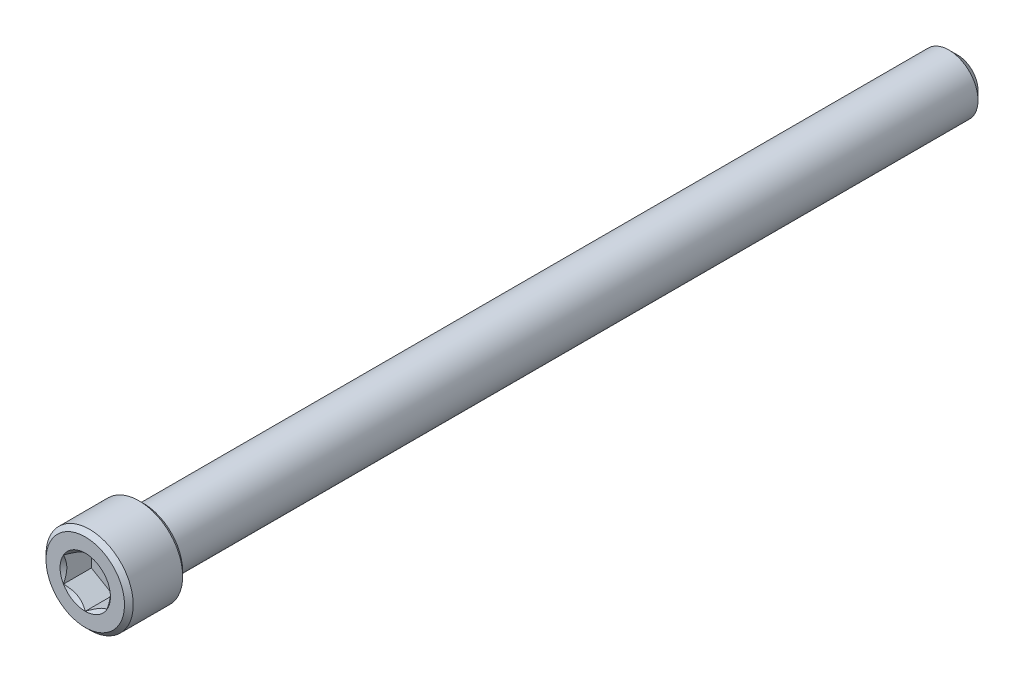
SolidWorks part; units mm, degrees
ref_plane "Front Plane" through (0, 0, 0) normal (0, 0, 1) x (1, 0, 0)
ref_plane "Top Plane" through (0, 0, 0) normal (0, 1, 0) x (1, 0, 0)
ref_plane "Right Plane" through (0, 0, 0) normal (1, 0, 0) x (0, 0, -1)
sketch "Sketch1" plane through (0, 0, 0) normal (1, 0, 0) x (0, 0, -1)
  line L0 (-47.625, 0) -> (47.625, 0) construction
  line L1 (-47.625, 0) -> (-47.625, 4.7625)
  line L2 (-47.625, 4.7625) -> (-41.275, 4.7625)
  line L3 (-41.275, 4.7625) -> (-41.275, 3.175)
  line L4 (-41.275, 3.175) -> (46.6725, 3.175)
  line L5 (47.5456, 3.3125) -> (48.1806, 2.2126) construction
  line L6 (48.1806, 2.2126) -> (48.8156, 3.3125) construction
  line L7 (48.8156, 3.3125) -> (47.5456, 3.3125) construction
  line L8 (46.6725, 3.175) -> (47.625, 2.2225)
  line L9 (47.625, 2.2225) -> (47.625, 0)
  line L10 (47.625, 3.175) -> (48.7362, 3.175) construction
  line L11 (48.1806, 3.3125) -> (48.1806, 3.175) construction
  line L12 (48.1806, 3.175) -> (48.1806, 2.3501) construction
  line L13 (48.1806, 2.3501) -> (48.1806, 2.2126) construction
  line L14 (48.1012, 2.3501) -> (48.26, 2.3501)
  line L15 (47.5853, 3.2437) -> (48.7759, 3.2437)
  line L16 (48.26, 2.3501) -> (48.7759, 3.2437)
  line L17 (48.1012, 2.3501) -> (47.5853, 3.2437)
  line L18 (-47.625, 2.3813) -> (-44.577, 2.3813)
  line L19 (-44.577, 2.3813) -> (-44.577, 0)
  line L20 (43.18, 3.175) -> (43.18, -3.175) construction
  point P20 (48.1806, 3.2437)
  point P22 (43.18, -3.175)
  point P23 (22.225, 3.175)
  point P28 (43.18, 0)
  dimension "Head Diameter" = 9.525
  dimension "Length" = 88.9
  dimension "Head Height" = 6.35
  dimension "Screw Size Decimal Equivalent" = 6.35
  dimension "D1" = 45
  dimension "Thread Pitch" = 1.27
  dimension "D3" = 0.1588
  dimension "D2" = 0.9525
  dimension "Drive Size" = 4.7625
  dimension "Drive Depth" = 3.048
  dimension "Minimum Thread Length" = 25.4
  dimension "D4" = 4.445
sketch "Sketch3" plane through (0, 0, 0) normal (1, 0, 0) x (0, 0, -1)
  line L0 (-47.625, 4.7625) -> (-47.625, 2.3813)
  line L1 (-47.625, 2.3813) -> (-44.577, 2.3813)
  line L2 (-44.577, 2.3813) -> (-44.577, 0)
  line L3 (-44.577, 0) -> (47.625, 0)
  line L4 (47.625, 0) -> (47.625, 2.2225)
  line L5 (47.625, 2.2225) -> (46.6725, 3.175)
  line L6 (46.6725, 3.175) -> (-41.275, 3.175)
  line L7 (-41.275, 3.175) -> (-41.275, 4.7625)
  line L8 (-41.275, 4.7625) -> (-47.625, 4.7625)
revolve "Revolve1" add sketch "Sketch3" angle 360 about L0
sketch "Sketch4" plane through (0, 0, 47.625) normal (0, 0, 1) x (1, 0, 0)
  line L1 (0, 2.7496) -> (-2.3813, 1.3748)
  line L2 (-2.3813, 1.3748) -> (-2.3813, -1.3748)
  line L3 (-2.3813, -1.3748) -> (0, -2.7496)
  line L4 (0, -2.7496) -> (2.3813, -1.3748)
  line L5 (2.3813, -1.3748) -> (2.3813, 1.3748)
  line L6 (2.3813, 1.3748) -> (0, 2.7496)
  circle A0 centre (0, 0) radius 2.3813 construction
extrude "Cut-Extrude1" cut sketch "Sketch4" against normal up to vertex (3.048 mm away) up to point (0, 2.3813, 44.577)
sketch "Sketch5" plane through (0, 0, 47.625) normal (0, 0, 1) x (1, 0, 0)
  circle A0 centre (0, 0) radius 2.7496
extrude "Cut-Extrude2" cut sketch "Sketch5" against normal up to next (3.048 mm away) draft 45
chamfer "Chamfer1" distance 0.4763 angle 45 2 edges at (0, -4.7625, 41.275) (0, -4.7625, 47.625)
split "Split1" [suppressed] bodies to split 106
sketch "Sketch6" [suppressed] plane through (0, 0, -47.625) normal (0, 0, -1) x (-1, 0, 0)
  circle A0 centre (0, 0) radius 3.175 construction
  circle A1 centre (0, 0) radius 3.175
curve "Helix/Spiral1" [suppressed] pitch 1.27 height 90.17 turns 71
sketch "Sketch7" [suppressed] plane through (0, 0, 0) normal (1, 0, 0) x (0, 0, -1)
  line L0 (48.1012, 2.3501) -> (48.26, 2.3501) construction
  line L1 (48.1012, 2.3501) -> (47.5853, 3.2437) construction
  line L2 (47.5853, 3.2437) -> (48.7759, 3.2437) construction
  line L3 (48.26, 2.3501) -> (48.7759, 3.2437) construction
  line L4 (48.1012, 2.3501) -> (48.26, 2.3501)
  line L5 (48.1012, 2.3501) -> (47.5853, 3.2437)
  line L6 (47.5853, 3.2437) -> (48.7759, 3.2437)
  line L7 (48.26, 2.3501) -> (48.7759, 3.2437)
sweep "Cut-Sweep1" [suppressed] cut profiles "Sketch7" path "Helix/Spiral1"
sketch "Sketch8" [suppressed] plane through (0, 0, 41.275) normal (0, 0, -1) x (-1, 0, 0)
  circle A0 centre (0, 0) radius 3.4925
  point P3 (0, 3.4925)
  dimension "D1" = 0.3175
extrude "Boss-Extrude1" [suppressed] add sketch "Sketch8" along normal blind 2.54 draft 60
sketch "Sketch9" [suppressed] plane through (0, 0, 41.275) normal (0, 0, -1) x (-1, 0, 0)
  circle A0 centre (0, 0) radius 3.175
extrude "Boss-Extrude2" [suppressed] add sketch "Sketch9" along normal up to vertex
equation "\"D3@Sketch1\" = \"Thread Pitch@Sketch1\" / 8"
equation "\"D2@Sketch1\" = \"Thread Pitch@Sketch1\" * .75"
equation "\"D4@Sketch1\" = \"Thread Pitch@Sketch1\" * 3.5"
equation "\"D1@Chamfer1\"=\"head diameter@sketch1\"*.05"
equation "\"D3@Helix/Spiral1\" = \"Length@Sketch1\" + \"Thread Pitch@Sketch1\""
equation "\"D4@Helix/Spiral1\" = \"Thread Pitch@Sketch1\""
equation "\"D1@Sketch8\" = \"Thread Pitch@Sketch1\" / 4"
